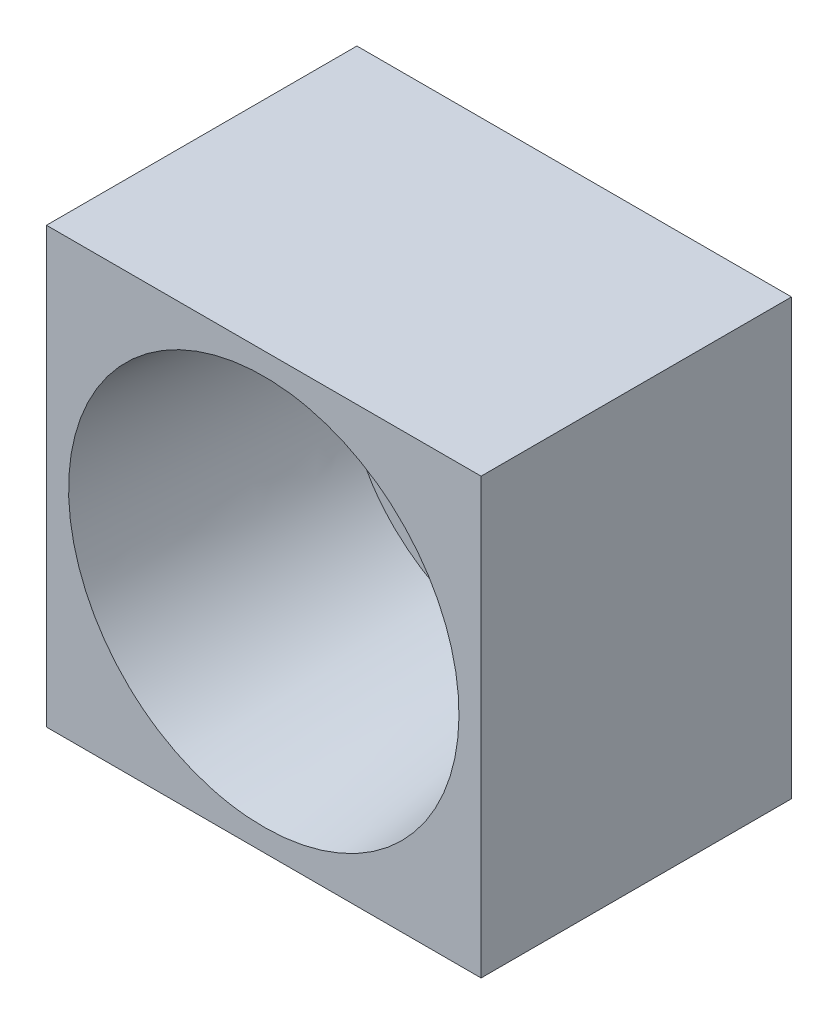
SolidWorks part; units mm, degrees
ref_plane "Front Plane" through (0, 0, 0) normal (0, 0, 1) x (1, 0, 0)
ref_plane "Top Plane" through (0, 0, 0) normal (0, 1, 0) x (1, 0, 0)
ref_plane "Right Plane" through (0, 0, 0) normal (1, 0, 0) x (0, 0, -1)
sketch "Sketch1" plane through (0, 0, 0) normal (0, 0, 1) x (1, 0, 0)
  line L1 (0, 0) -> (-70, 0)
  line L2 (0, 0) -> (0, -70)
  line L3 (0, -70) -> (-70, -70)
  line L4 (-70, 0) -> (-70, -70)
  dimension "D2" = 70
extrude "Boss-Extrude1" add sketch "Sketch1" along normal blind 50
ref_plane "Plane1" through (0, 0, 10) normal (0, 0, 1) x (1, 0, 0)
sketch "Sketch2" plane through (0, 0, 10) normal (0, 0, 1) x (1, 0, 0)
  line L0 (-35, 0) -> (-35, -70) construction
  line L1 (0, 0) -> (-70, 0) construction
  line L2 (-70, -70) -> (0, -70) construction
  circle A0 centre (-35, -35) radius 27
  dimension "D1" = 54
ref_plane "Plane2" through (-35, 0, 0) normal (1, 0, 0) x (0, 0, -1)
sketch "Sketch6" plane through (-35, 0, 0) normal (1, 0, 0) x (0, 0, -1)
  line L0 (-10, -8) -> (-50, -3.0886)
  line L1 (-10, 0) -> (-10, -70) construction
  line L2 (-10, -8) -> (-10, -62) construction
  line L3 (-50, -70) -> (-50, 0) construction
sketch "Sketch7" plane through (0, 0, 50) normal (0, 0, 1) x (1, 0, 0)
  circle A1 centre (-35, -35) radius 31.4407
loft "Cut-Loft1" cut profiles "Sketch2", "Sketch7" connector at (-19.3087, -13.0276, 10) connector at (-22.0797, -6.3368, 50)
sketch "Sketch8" plane through (0, 0, 10) normal (0, 0, 1) x (1, 0, 0)
  line L0 (-35, -35) -> (-57.1207, -35) construction
  line L1 (-35, -35) -> (-14.7964, -35) construction
  line L2 (-35, -35) -> (-35, -53.1762) construction
  circle A0 centre (-27.5, -35) radius 2.5
  circle A1 centre (-42.5, -35) radius 2.5
  dimension "D1" = 5
  dimension "7.5" = 7.5
extrude "Cut-Extrude1" cut sketch "Sketch8" against normal blind 50
